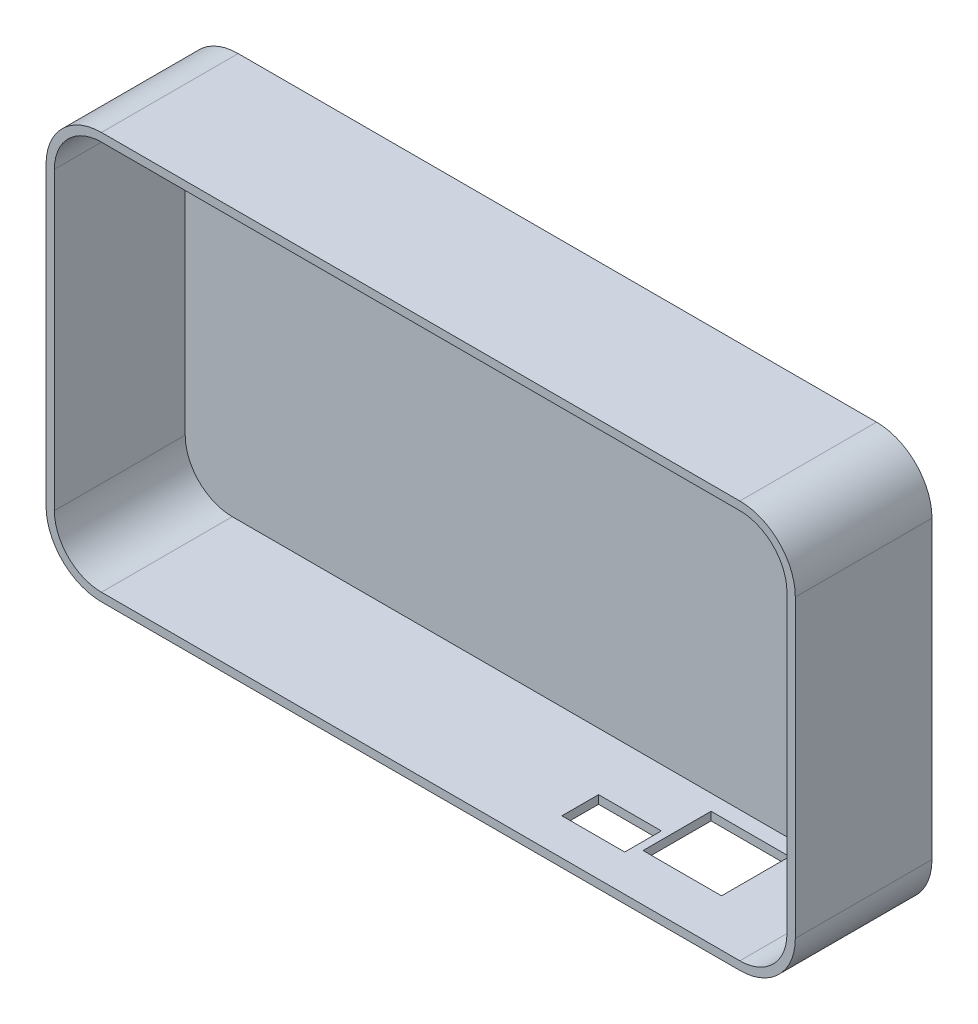
SolidWorks part; units mm, degrees
ref_plane "Alzado" through (0, 0, 0) normal (0, 0, 1) x (1, 0, 0)
ref_plane "Planta" through (0, 0, 0) normal (0, 1, 0) x (1, 0, 0)
ref_plane "Vista lateral" through (0, 0, 0) normal (1, 0, 0) x (0, 0, -1)
sketch "Croquis1" plane through (0, 0, 0) normal (0, 0, 1) x (1, 0, 0)
  line L0 (9, 76.1) -> (131, 76.1)
  line L1 (9, 0) -> (131, 0)
  line L2 (0, 9) -> (0, 65.5)
  line L3 (9, 74.5) -> (131, 74.5)
  line L4 (140, 9) -> (140, 65.5)
  line L5 (141.6, 9) -> (141.6, 65.5)
  line L6 (9, -1.6) -> (131, -1.6)
  line L7 (-1.6, 9) -> (-1.6, 65.5)
  arc A0 (131, 74.5) -> (140, 65.5) centre (131, 65.5) cw
  arc A1 (131, 0) -> (140, 9) centre (131, 9) ccw
  arc A2 (9, 0) -> (0, 9) centre (9, 9) cw
  arc A3 (0, 65.5) -> (9, 74.5) centre (9, 65.5) cw
  arc A4 (131, 76.1) -> (141.6, 65.5) centre (131, 65.5) cw
  arc A5 (131, -1.6) -> (141.6, 9) centre (131, 9) ccw
  arc A6 (9, -1.6) -> (-1.6, 9) centre (9, 9) cw
  arc A7 (-1.6, 65.5) -> (9, 76.1) centre (9, 65.5) cw
  point P9 (140, 0)
  point P12 (0, 0)
  point P15 (0, 74.5)
  dimension "D3" = 9
  dimension "D1" = 140
  dimension "D2" = 74.5
  dimension "D4" = 1.6
extrude "pared" add sketch "Croquis1" along normal blind 25
sketch "Croquis2" plane through (0, -1.6, 0) normal (0, -1, 0) x (1, 0, 0)
  line L0 (0, 25) -> (0, 0) construction
  line L1 (140, 25) -> (140, 0) construction
  line L2 (9, 25) -> (-1.6, 25) construction
  line L3 (-1.6, 25) -> (-1.6, 0) construction
  line L4 (-1.6, 0) -> (9, 0) construction
  line L5 (9, 0) -> (131, 0) construction
  line L6 (131, 0) -> (141.6, 0) construction
  line L7 (141.6, 25) -> (141.6, 0) construction
  line L8 (141.6, 25) -> (131, 25) construction
  line L9 (9, 25) -> (131, 25) construction
  line L10 (0, 25) -> (0, 0)
  line L11 (140, 25) -> (140, 0)
  line L12 (9, 25) -> (-1.6, 25)
  line L13 (-1.6, 25) -> (-1.6, 0)
  line L14 (-1.6, 0) -> (9, 0)
  line L15 (9, 0) -> (131, 0)
  line L16 (131, 0) -> (141.6, 0)
  line L17 (141.6, 25) -> (141.6, 0)
  line L18 (141.6, 25) -> (131, 25)
  line L19 (9, 25) -> (131, 25)
  line L21 (103.5, 16) -> (118.5, 16)
  line L22 (103.5, 16) -> (103.5, 3)
  line L23 (103.5, 3) -> (118.5, 3)
  line L24 (118.5, 16) -> (118.5, 3)
  line L25 (90, 18) -> (102, 18)
  line L26 (90, 18) -> (90, 11)
  line L27 (90, 11) -> (102, 11)
  line L28 (102, 18) -> (102, 11)
  dimension "D1" = 3
  dimension "D2" = 13
  dimension "D3" = 21.5
  dimension "D4" = 15
  dimension "D5" = 12
  dimension "D6" = 7
  dimension "D7" = 50
  dimension "D8" = 11
extrude "conectores" cut sketch "Croquis2" against normal up to next contours L24 L21 L22 L23 | L28 L25 L26 L27 region at (111, -1.6, 9.5) region at (96, -1.6, 14.5)
extrude "base frente" add sketch "Croquis1<2>" against normal blind 1.12 contours A6 L7 A7 L0 A4 L5 A5 L6
sketch "Croquis1<2>" plane through (0, 0, 0) normal (0, 0, 1) x (1, 0, 0) same geometry as "Croquis1"
sketch "Croquis3" plane through (0, 0, 0) normal (0, 0, 1) x (1, 0, 0)
  line L0 (131, 35.5) -> (133, 35.5)
  line L1 (131.5, 54) -> (132.5, 54)
  line L2 (131, 53.5) -> (131, 29.5)
  line L3 (131.5, 29) -> (132.5, 29)
  line L4 (140, 9) -> (140, 65.5)
  line L5 (131, 74.5) -> (9, 74.5)
  line L6 (0, 65.5) -> (0, 9)
  line L7 (9, 0) -> (131, 0)
  line L8 (140, 9) -> (140, 65.5)
  line L9 (131, 74.5) -> (9, 74.5)
  line L10 (0, 65.5) -> (0, 9)
  line L11 (9, 0) -> (131, 0)
  line L12 (133, 53.5) -> (133, 29.5)
  line L13 (131.5, 28) -> (132.5, 28)
  line L14 (131, 27.5) -> (131, 13.5)
  line L15 (131.5, 13) -> (132.5, 13)
  line L16 (133, 27.5) -> (133, 13.5)
  line L17 (131, 34.5) -> (133, 34.5)
  line L18 (131, 42) -> (133, 42)
  line L19 (131, 41) -> (133, 41)
  line L20 (131, 48.5) -> (133, 48.5)
  line L21 (131, 47.5) -> (133, 47.5)
  line L22 (131, 41.5) -> (133, 41.5) construction
  line L23 (131, 35.5) -> (131, 42) construction
  arc A0 (131.5, 54) -> (131, 53.5) centre (131.5, 53.5) ccw
  arc A1 (132.5, 54) -> (133, 53.5) centre (132.5, 53.5) cw
  arc A2 (131, 29.5) -> (131.5, 29) centre (131.5, 29.5) ccw
  arc A3 (132.5, 29) -> (133, 29.5) centre (132.5, 29.5) ccw
  arc A4 (131, 0) -> (140, 9) centre (131, 9) ccw
  arc A5 (140, 65.5) -> (131, 74.5) centre (131, 65.5) ccw
  arc A6 (9, 74.5) -> (0, 65.5) centre (9, 65.5) ccw
  arc A7 (0, 9) -> (9, 0) centre (9, 9) ccw
  arc A8 (131, 0) -> (140, 9) centre (131, 9) ccw
  arc A9 (140, 65.5) -> (131, 74.5) centre (131, 65.5) ccw
  arc A10 (9, 74.5) -> (0, 65.5) centre (9, 65.5) ccw
  arc A11 (0, 9) -> (9, 0) centre (9, 9) ccw
  arc A12 (131.5, 28) -> (131, 27.5) centre (131.5, 27.5) ccw
  arc A13 (132.5, 28) -> (133, 27.5) centre (132.5, 27.5) cw
  arc A14 (131, 13.5) -> (131.5, 13) centre (131.5, 13.5) ccw
  arc A15 (132.5, 13) -> (133, 13.5) centre (132.5, 13.5) ccw
  point P32 (133, 28)
  point P37 (133, 13)
  dimension "D8" = 0.5
  dimension "D2" = 2
  dimension "D3" = 7
  dimension "D4" = 25
  dimension "D5" = 29
  dimension "D6" = 1
  dimension "D7" = 15
  dimension "D11" = 6.5
  dimension "D1" = 0
  dimension "D9" = 1
  dimension "D10" = 3
extrude "luces" cut sketch "Croquis3" against normal up to next contours L15 A15 L16 A13 L13 A12 L14 A14 | L3 A3 L12 L17 L2 A2 | L19 L2 L0 L12 | L21 L2 L18 L12 | A1 L1 A0 L2 L20 L12 region at (132, 38.25, 0) region at (132, 31.776, 0) region at (132, 44.75, 0) region at (132, 51.224, 0) region at (132, 20.5, 0)
sketch "Croquis4" plane through (0, 0, 0) normal (0, 1, 0) x (1, 0, 0)
  line L0 (40.0104, -2.6878) -> (40.0104, -21.081)
  line L1 (58.1341, -20.0402) -> (40.0104, -20.0402)
  line L2 (58.1341, -20.0402) -> (58.1341, -12.7932)
  line L3 (58.1341, -12.7932) -> (40.0104, -12.7932)
  line L4 (40.0104, -20.0402) -> (40.0104, -12.7932)
  line L5 (58.1341, -2.6878) -> (58.1341, -21.081)
  line L6 (49, 0) -> (49, -25) construction
  line L7 (9, 0) -> (131, 0) construction
  line L8 (9, -25) -> (131, -25) construction
  line L9 (9, -25) -> (9, 0) construction
  dimension "D1" = 40
sketch "Croquis5" plane through (0, 0, 0) normal (0, 0, 1) x (1, 0, 0)
  line L0 (39, 0) -> (39, 2)
  line L1 (9, 0) -> (131, 0) construction
  line L2 (39, 2) -> (42, 2)
  line L3 (42, 2) -> (42, 3.2)
  line L4 (42, 3.2) -> (38, 3.2)
  line L5 (38, 3.2) -> (37, 0)
  line L6 (37, 0) -> (39, 0)
  line L7 (49, 7.3739) -> (49, -3.1931) construction
  line L8 (61, 0) -> (59, 0)
  line L9 (60, 3.2) -> (61, 0)
  line L10 (56, 3.2) -> (60, 3.2)
  line L11 (56, 2) -> (56, 3.2)
  line L12 (59, 2) -> (56, 2)
  line L13 (59, 0) -> (59, 2)
  point P16 (80.5395, 4.2963)
  point P17 (82.8542, 0)
  point P18 (85.0992, 0)
  point P19 (82.6558, 3.2)
  point P21 (49, -3.1931)
  dimension "D1" = 2
  dimension "D2" = 1.2
  dimension "D3" = 3
  dimension "D4" = 20
  dimension "D5" = 2
  dimension "D6" = 40
  dimension "D7" = 4
